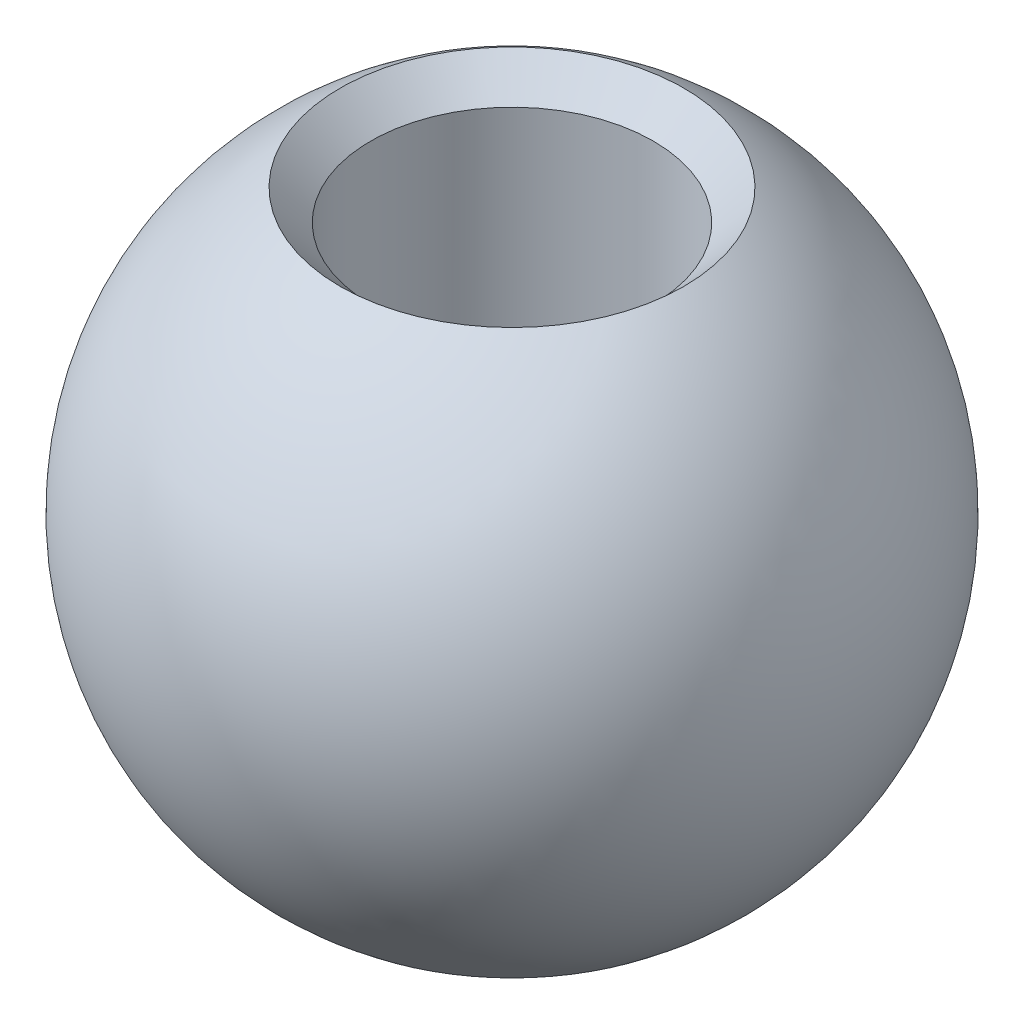
SolidWorks part; units mm, degrees
material "ASTM A36 Steel"
ref_plane "Front Plane" through (0, 0, 0) normal (0, 0, 1) x (1, 0, 0)
ref_plane "Top Plane" through (0, 0, 0) normal (0, 1, 0) x (1, 0, 0)
ref_plane "Right Plane" through (0, 0, 0) normal (1, 0, 0) x (0, 0, -1)
sketch "Sketch1" plane through (0, 0, 0) normal (0, 0, 1) x (1, 0, 0)
  line L0 (0, 0) -> (0, 7) construction
  line L1 (0, 6.3246) -> (3, 6.3246)
  line L2 (0, 0) -> (7, 0) construction
  line L3 (3, 6.3246) -> (3, -6.3246)
  circle A0 centre (0, 0) radius 7
  dimension "D1" = 14
  dimension "D2" = 3
revolve "Revolve1" add sketch "Sketch1" angle 360 about L0
chamfer "Chamfer1" distance 1 angle 45 2 edges at (0, -6.3246, -3) (0, 6.3246, -3)
